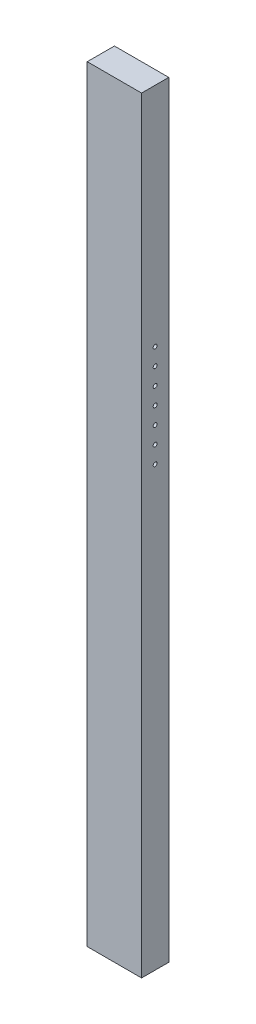
SolidWorks part; units mm, degrees
material "Sapin"
ref_plane "Plan de face" through (0, 0, 0) normal (0, 0, 1) x (1, 0, 0)
ref_plane "Plan de dessus" through (0, 0, 0) normal (0, 1, 0) x (1, 0, 0)
ref_plane "Plan de droite" through (0, 0, 0) normal (1, 0, 0) x (0, 0, -1)
sketch "Esquisse1" plane through (0, 0, 0) normal (0, 0, 1) x (1, 0, 0)
  line L1 (-24, -338.5) -> (24, -338.5)
  line L2 (-24, -338.5) -> (-24, 338.5)
  line L3 (-24, 338.5) -> (24, 338.5)
  line L4 (24, -338.5) -> (24, 338.5)
  line L5 (-24, -338.5) -> (24, 338.5) construction
  line L6 (-24, 338.5) -> (24, -338.5) construction
  point P0 (0, 0)
  dimension "D1" = 48
  dimension "D2" = 677
extrude "Boss.-Extru.1" add sketch "Esquisse1" along normal mid plane 24
sketch "Esquisse2" plane through (24, 0, 0) normal (1, 0, 0) x (0, 0, -1)
  line L0 (-12, -338.5) -> (12, -338.5) construction
  line L1 (-12, 338.5) -> (12, 338.5) construction
  circle A0 centre (0, 48.5) radius 1.75
  point P2 (0, 0)
  point P5 (0, -338.5)
  point P6 (0, -40.005)
  point P9 (0, 38.3014)
  dimension "D1" = 3.5
  dimension "D2" = 290
extrude "Enlèv. mat.-Extru.1" cut sketch "Esquisse2" against normal through all
pattern_linear "Répétition linéaire1" count 7 spacing 15 along (0, 1, 0) of "Enlèv. mat.-Extru.1"
